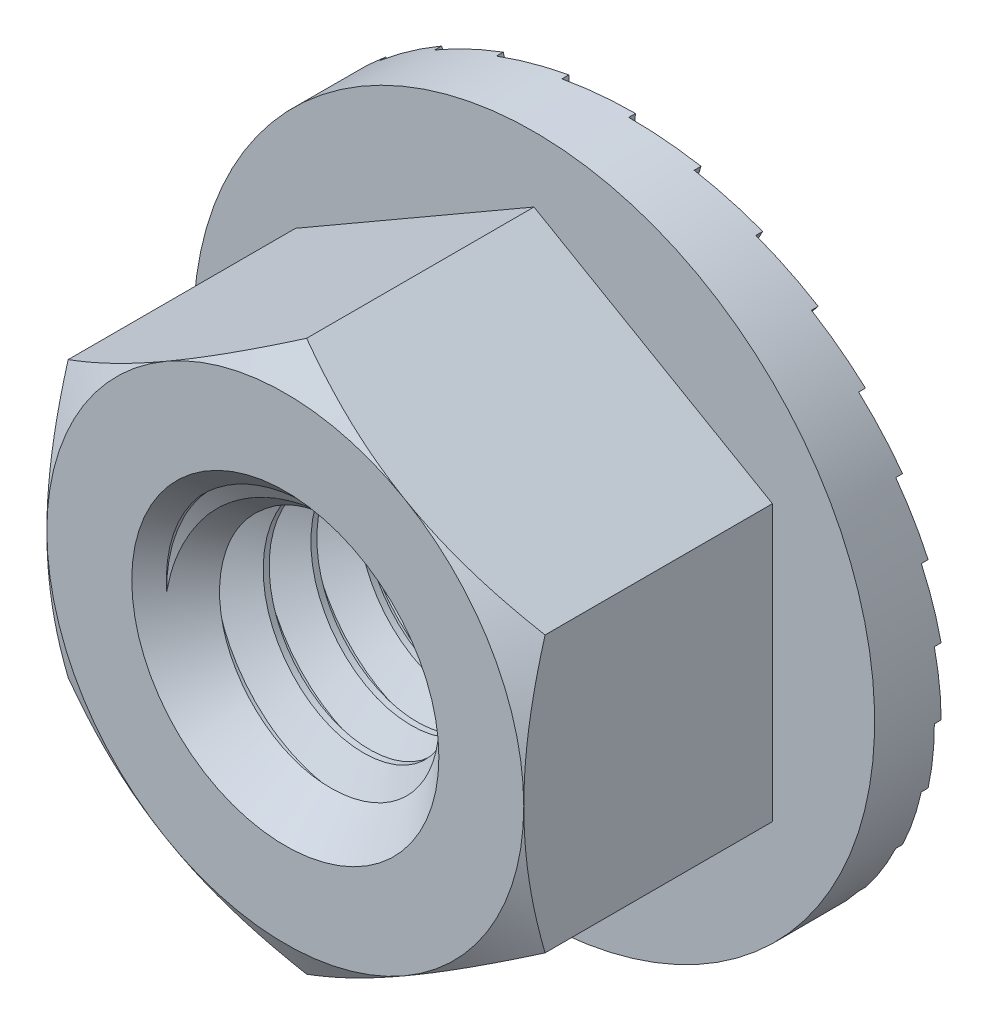
SolidWorks part; units mm, degrees
ref_plane "Front Plane" through (0, 0, 0) normal (0, 0, 1) x (1, 0, 0)
ref_plane "Top Plane" through (0, 0, 0) normal (0, 1, 0) x (1, 0, 0)
ref_plane "Right Plane" through (0, 0, 0) normal (1, 0, 0) x (0, 0, -1)
sketch "Sketch1" plane through (0, 0, 0) normal (0, 0, 1) x (1, 0, 0)
  line L1 (0, 4.0415) -> (-3.5, 2.0207)
  line L2 (-3.5, 2.0207) -> (-3.5, -2.0207)
  line L3 (-3.5, -2.0207) -> (0, -4.0415)
  line L4 (0, -4.0415) -> (3.5, -2.0207)
  line L5 (3.5, -2.0207) -> (3.5, 2.0207)
  line L6 (3.5, 2.0207) -> (0, 4.0415)
  circle A0 centre (0, 0) radius 3.5 construction
  dimension "Hex" = 7
extrude "Extrude1" add sketch "Sketch1" against normal blind 4.65
sketch "Sketch13" plane through (0, 0, -4.65) normal (0, 0, -1) x (-1, 0, 0)
  circle A0 centre (0, 0) radius 5
  dimension "Flange od" = 10
extrude "Extrude3" add sketch "Sketch13" against normal blind 1
sketch "Sketch2" plane through (0, 0, 0) normal (0, 0, 1) x (1, 0, 0)
  circle A0 centre (0, 0) radius 3.5 construction
  circle A1 centre (0, 0) radius 3.5
extrude "Cut-Extrude1" cut sketch "Sketch2" against normal through all draft 60 flip side to cut
sketch "Sketch4" plane through (0, 0, 0) normal (0, 0, 1) x (1, 0, 0)
  circle A0 centre (0, 0) radius 2
  dimension "Thread Dia" = 4
extrude "Cut-Extrude3" cut sketch "Sketch4" against normal through all
sketch "Sketch7" plane through (0, 0, 0) normal (0, 0, 1) x (1, 0, 0)
  circle A4 centre (0, 0) radius 2.254
  circle A5 centre (0, 0) radius 2.254
  dimension "D1" = 0.254
sketch "Sketch8" plane through (0, 0, -4.65) normal (0, 0, -1) x (-1, 0, 0)
  circle A1 centre (0, 0) radius 2.254
  circle A2 centre (0, 0) radius 2.254 construction
sketch "Sketch5" plane through (0, 0, 0) normal (0, 0, 1) x (1, 0, 0)
  circle A0 centre (0, 0) radius 2 construction
  circle A1 centre (0, 0) radius 2
curve "Helix/Spiral1" pitch 0.7 height 5.35 radius 2 centre (0, 0, 0) axis (0, 0, -1) start towards (0, 1, 0) parameters "pitch"=0.7
sketch "Sketch9" plane through (0, 0, 0) normal (1, 0, 0) x (0, 0, -1)
  line L0 (-0.35, 2) -> (-0.2625, 2)
  line L1 (-0.2625, 2) -> (0, 1.5453)
  line L2 (-0.35, 2) -> (-0.6125, 1.5453)
  line L3 (-0.6125, 1.5453) -> (0, 1.5453)
  line L4 (-0.3062, 2) -> (-0.3062, 1.5453) construction
  line L5 (-0.4812, 1.7727) -> (-0.1312, 1.7727) construction
  line L7 (0, 1.5453) -> (0, 2) construction
  line L8 (0, 2) -> (0, -2) construction
  dimension "D1" = 0.0875
  dimension "D2" = 0.35
  dimension "D3" = 60
sketch "Sketch12" plane through (0, 0, 0) normal (0, 0, 1) x (1, 0, 0)
  circle A0 centre (0, 0) radius 1.5453
  circle A1 centre (0, 0) radius 2 construction
  circle A2 centre (0, 0) radius 2
extrude "Extrude2" add sketch "Sketch12" against normal up to surface (4.65 mm away) up to face at (2, 0, -4.65)
sweep "Cut-Sweep1" cut profiles "Sketch9" path "Helix/Spiral1" align with end faces yes
extrude "Cut-Extrude6" cut sketch "Sketch7" against normal through all draft 45
extrude "Cut-Extrude7" cut sketch "Sketch8" against normal through all draft 45
sketch "Sketch14" plane through (0, 0, -4.65) normal (0, 0, -1) x (-1, 0, 0)
  circle A4 centre (0, 0) radius 2.754
  circle A5 centre (0, 0) radius 2.754
  dimension "D1" = 0.5
extrude "Cut-Extrude8" cut sketch "Sketch14" against normal blind 0.1 flip side to cut
sketch "Sketch15" plane through (0, 0, -4.55) normal (0, 0, -1) x (-1, 0, 0)
  line L0 (-0.2699, 2.7407) -> (-0.4901, 4.9759)
  line L1 (0.2699, 2.7407) -> (0.4901, 4.9759)
  line L2 (0, 0) -> (0.2699, 2.7407) construction
  line L3 (0, 0) -> (-0.2699, 2.7407) construction
  circle A0 centre (0, 0) radius 5 construction
  circle A1 centre (0, 0) radius 2.754 construction
  arc A2 (0.4901, 4.9759) -> (-0.4901, 4.9759) centre (0, 0) ccw
  arc A3 (0.2699, 2.7407) -> (-0.2699, 2.7407) centre (0, 0) ccw
  dimension "D1" = 11.25
extrude "Extrude4" add sketch "Sketch15" along normal up to surface (0.1 mm away) separate body up to face at (-2.254, 0, -4.65)
sketch "Sketch16" plane through (0, 0, 0) normal (0, 1, 0) x (1, 0, 0)
  line L0 (-0.4901, 4.55) -> (0.4901, 4.65)
  line L4 (-0.4901, 4.55) -> (0.4901, 4.55)
  line L5 (0.4901, 4.55) -> (0.4901, 4.65)
  line L6 (0.4901, 4.65) -> (-0.4901, 4.65)
  line L7 (-0.4901, 4.65) -> (-0.4901, 4.55)
  line L8 (-0.4901, 4.55) -> (0.4901, 4.55) construction
  line L9 (0.4901, 4.55) -> (0.4901, 4.65) construction
  line L10 (0.4901, 4.65) -> (-0.4901, 4.65)
  line L11 (-0.4901, 4.65) -> (-0.4901, 4.55)
  dimension "D1" = 0
extrude "Cut-Extrude9" cut sketch "Sketch16" along normal through all
pattern_circular "CirPattern1" count 32 over 360 about axis through (0, 0, -7.1127) along (0, 0, 1) of bodies 119
combine bodies "Combine1" operation type add bodies to combine 117 119 120 121 122 123 124 125 126 127 128 129 130 131 132 133 134 135 136 137 139 140 141 142 143 144 145 146 147 148 149 150 151
sketch "Sketch17" plane through (0, 0, 0) normal (1, 0, 0) x (0, 0, -1)
  line L0 (4.65, 5) -> (4.65, -5) construction
  line L1 (3.65, 5) -> (3.65, -5) construction
  dimension "D1" = 1
sketch "Sketch18" plane through (0, 0, -3.65) normal (0, 0, 1) x (1, 0, 0)
  circle A0 centre (0, 0) radius 5
  circle A1 centre (0, 0) radius 5 construction
equation "\"D2@Sketch9\" = \"pitch@Helix/Spiral1\"*.5"
equation "\"D3@Helix/Spiral1\" = \"pitch@Helix/Spiral1\"+\"Height@Extrude1\""
equation "\"D1@Sketch9\" = \"pitch@Helix/Spiral1\"*.125"
equation "\"D1@Cut-Extrude8\" = \"flange thickness@Extrude3\"*.1"
equation "\"D1@Sketch17\" = \"flange thickness@Extrude3\""
